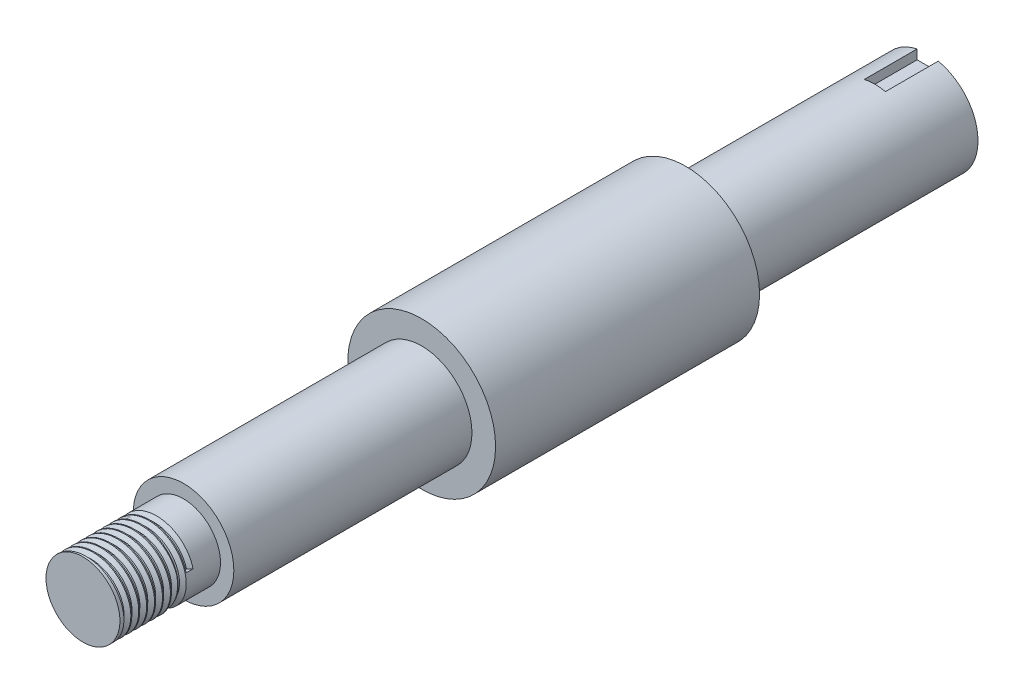
SolidWorks part; units mm, degrees
material "AISI 1020"
ref_plane "Front Plane" through (0, 0, 0) normal (0, 0, 1) x (1, 0, 0)
ref_plane "Top Plane" through (0, 0, 0) normal (0, 1, 0) x (1, 0, 0)
ref_plane "Right Plane" through (0, 0, 0) normal (1, 0, 0) x (0, 0, -1)
sketch "Sketch Spindle Skeleton" plane through (0, 0, 0) normal (1, 0, 0) x (0, 0, -1)
  line L0 (-95.847, -9.525) -> (-140.95, -9.525)
  line L5 (-1000, 0) -> (49000, 0)
  line L6 (0, -9.525) -> (0, 9.525)
  line L13 (0, 9.525) -> (-45.847, 9.525)
  line L26 (-45.847, 9.525) -> (-45.847, 14)
  line L27 (-45.847, 14) -> (-95.847, 14)
  line L32 (-95.847, 14) -> (-95.847, 9.525)
  line L34 (-160, 7) -> (-160, -7)
  line L36 (-95.847, -9.525) -> (-95.847, -14)
  line L37 (-95.847, -14) -> (-45.847, -14)
  line L38 (-45.847, -14) -> (-45.847, -9.525)
  line L39 (0, -9.525) -> (-45.847, -9.525)
  line L40 (-25.305, 36.5125) -> (-16.305, 36.5125)
  line L41 (-111.341, 22.6187) -> (-95.847, 22.6187)
  line L42 (-111.341, 22.6187) -> (-111.341, -22.6187)
  line L43 (-111.341, -22.6187) -> (-95.847, -22.6187)
  line L44 (-95.847, 22.6187) -> (-95.847, -22.6187)
  line L45 (-111.341, 22.6187) -> (-95.847, -22.6187) construction
  line L46 (-111.341, -22.6187) -> (-95.847, 22.6187) construction
  line L47 (-30.353, 22.6187) -> (-45.847, 22.6187)
  line L48 (-30.353, 22.6187) -> (-30.353, -22.6187)
  line L49 (-30.353, -22.6187) -> (-45.847, -22.6187)
  line L50 (-45.847, 22.6187) -> (-45.847, -22.6187)
  line L51 (-30.353, 22.6187) -> (-45.847, -22.6187) construction
  line L52 (-30.353, -22.6187) -> (-45.847, 22.6187) construction
  line L59 (-16.305, 36.5125) -> (-16.305, -36.5125)
  line L60 (-16.305, -36.5125) -> (-25.305, -36.5125)
  line L61 (-25.305, -22.6187) -> (-27.305, -22.6187)
  line L62 (-27.305, -22.6187) -> (-27.305, -12.5)
  line L63 (-27.305, -12.5) -> (-25.305, -12.5)
  line L64 (-25.305, -12.5) -> (-25.305, 12.5)
  line L65 (-25.305, 12.5) -> (-27.305, 12.5)
  line L66 (-27.305, 12.5) -> (-27.305, 22.6187)
  line L67 (-27.305, 22.6187) -> (-25.305, 22.6187)
  line L68 (-25.305, 22.6187) -> (-25.305, 36.5125)
  line L69 (-25.305, -22.6187) -> (-25.305, -36.5125)
  line L71 (-119.469, 36.5125) -> (-26.305, 36.5125)
  line L72 (-119.469, 36.5125) -> (-119.469, -36.5125)
  line L73 (-119.469, -36.5125) -> (-26.305, -36.5125)
  line L74 (-26.305, 36.5125) -> (-26.305, -36.5125)
  line L75 (-119.469, 36.5125) -> (-26.305, -36.5125) construction
  line L76 (-119.469, -36.5125) -> (-26.305, 36.5125) construction
  line L77 (-140.95, -9.525) -> (-140.95, -7)
  line L78 (-140.95, -7) -> (-160, -7)
  line L79 (-95.847, 9.525) -> (-140.95, 9.525)
  line L80 (-140.95, 7) -> (-160, 7)
  line L81 (-140.95, 9.525) -> (-140.95, 7)
  line L82 (-118.3985, 9.525) -> (-118.3985, -9.525) construction
  line L83 (-22.9235, 9.525) -> (-22.9235, -9.525) construction
  line L96 (-119.469, 36.5125) -> (-134.709, 36.5125)
  line L98 (-119.469, -36.5125) -> (-134.709, -36.5125)
  line L99 (-134.709, 36.5125) -> (-134.709, -36.5125)
  line L110 (-119.469, 36.5125) -> (-119.469, -36.5125)
  point P3 (0, 0)
  point P18 (-103.594, 0)
  point P24 (-38.1, 0)
  point P29 (-72.887, 0)
  point P48 (-16.305, 30.5656)
  point P58 (0, 0)
  point P59 (0, 0)
  point P70 (-134.709, 31.75)
revolve "Revolve Spindle" add sketch "Sketch Spindle Skeleton" angle 360 about L5
thread "Chuck Thread" pitch 1.5 start angle 0, offset 0, length 12.7, pitch 1.5, diameter 14
ref_plane "Plane2" through (-7, 0, 160) normal (0, -1, 0) x (-1, 0, 0)
sketch "Thread Profile2" plane through (-7, 0, 160) normal (0, -1, 0) x (-1, 0, 0)
  line L0 (0, 0) -> (0, 1.5) construction
  line L11 (0, 0) -> (0, 1.3125)
  line L12 (0, 1.3125) -> (-0.8119, 0.8437)
  line L13 (-0.8119, 0.8437) -> (-0.8119, 0.4687)
  line L15 (-0.8119, 0.4687) -> (0, 0)
  line L17 (-0.8119, 0.6562) -> (0, 0.6562) construction
  point P2 (0, 0)
  dimension "Pitch" = 1.5
  dimension "Profile_Angle" = 60
  dimension "Profile_Land" = 0.375
  dimension "Profile_Height" = 0.8119
sketch "Thread Slot Sketch" plane through (0, 0, 0) normal (1, 0, 0) x (0, 0, -1)
  line L0 (-145.9866, 1.4554) -> (-147.2991, 1.4554) construction
  line L1 (-145.9866, 1.4554) -> (-147.2991, 1.4554)
  line L2 (-140.95, 7) -> (-148.5, 7) construction
  line L3 (-140.95, 9.525) -> (-140.95, -9.525) construction
  line L6 (-160, 7) -> (-160, -7) construction
  line L7 (-140.95, 7) -> (-146.3125, 7) construction
  circle A0 centre (-148.5, 7) radius 0.5
  dimension "D1" = 1
  dimension "D2" = 11.5
revolve "Thread Slot" cut sketch "Thread Slot Sketch" angle 360 about L5
sketch "Sketch Key" plane through (0, 0, 0) normal (0, 0, -1) x (-1, 0, 0)
  line L0 (0, 8.525) -> (0, 0) construction
  line L1 (-2, 7.525) -> (2, 7.525)
  line L2 (-2, 7.525) -> (-2, 9.525)
  line L3 (-2, 9.525) -> (2, 9.525)
  line L4 (2, 7.525) -> (2, 9.525)
  line L5 (-2, 7.525) -> (2, 9.525) construction
  line L6 (-2, 9.525) -> (2, 7.525) construction
  circle A1 centre (0, 0) radius 9.525
  circle A2 centre (0, 0) radius 9.525
  point P0 (0, 8.525)
  dimension "D2" = 4
  dimension "D3" = 2
  dimension "D1" = 0
extrude "Key Cut" cut sketch "Sketch Key" against normal blind 10 contours L3 L4 L1 L2
